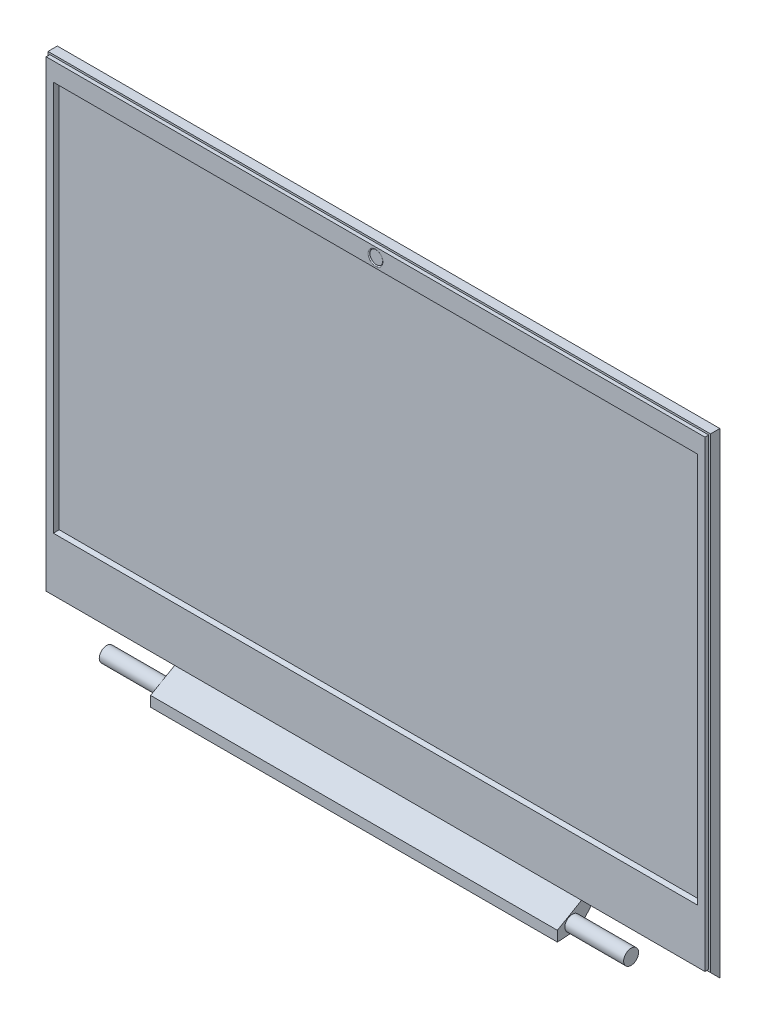
SolidWorks part; units mm, degrees
ref_plane "前视基准面" through (0, 0, 0) normal (0, 0, 1) x (1, 0, 0)
ref_plane "上视基准面" through (0, 0, 0) normal (0, 1, 0) x (1, 0, 0)
ref_plane "右视基准面" through (0, 0, 0) normal (1, 0, 0) x (0, 0, -1)
other "Configuration Table"
sketch "草图1" plane through (0, 0, 0) normal (1, 0, 0) x (0, 0, -1)
  line L0 (0, 0) -> (0, 255)
  line L1 (0, 255) -> (-5, 255)
  line L2 (-5, 255) -> (-5, 5)
  line L3 (-5, 5) -> (0, 0)
  dimension "D1" = 5
  dimension "D2" = 250
  dimension "D3" = 135
extrude "凸台-拉伸1" add sketch "草图1" along normal mid plane 355
sketch "草图3" plane through (0, 0, 0) normal (1, 0, 0) x (0, 0, -1)
  line L0 (0, 0) -> (-6.5838, -7.5269)
  line L1 (-6.5838, -7.5269) -> (-18.557, -8.3272)
  line L2 (-18.557, -8.3272) -> (-18.557, -2.8272)
  line L5 (-18.557, -2.8272) -> (-5, 5)
  line L6 (-5, 255) -> (-5, 5) construction
  line L7 (-5, 5) -> (0, 0)
  dimension "D1" = 135
  dimension "D2" = 5.5
  dimension "D3" = 12
  dimension "D4" = 10
  dimension "D5" = 120
extrude "凸台-拉伸2" add sketch "草图3" along normal mid plane 218
sketch "草图4" plane through (0, 0, 5) normal (0, 0, 1) x (1, 0, 0)
  line L6 (-177.5, 255) -> (-177.5, 5)
  line L7 (-177.5, 5) -> (-109, 5)
  line L8 (-109, 5) -> (109, 5)
  line L9 (109, 5) -> (177.5, 5)
  line L10 (177.5, 5) -> (177.5, 255)
  line L11 (177.5, 255) -> (-177.5, 255)
  line L12 (-177.5, 255) -> (-177.5, 5)
  line L13 (-177.5, 5) -> (-109, 5)
  line L14 (-109, 5) -> (109, 5)
  line L15 (109, 5) -> (177.5, 5)
  line L16 (177.5, 5) -> (177.5, 255)
  line L17 (177.5, 255) -> (-177.5, 255)
  dimension "D1" = 0
extrude "凸台-拉伸3" add sketch "草图4" along normal blind 2
sketch "草图5" plane through (0, 0, 7) normal (0, 0, 1) x (1, 0, 0)
  line L4 (177.5, 255) -> (-177.5, 255)
  line L5 (-177.5, 255) -> (-177.5, 5)
  line L6 (-177.5, 5) -> (177.5, 5)
  line L7 (177.5, 5) -> (177.5, 255)
  line L8 (177.5, 255) -> (-177.5, 255)
  line L9 (-177.5, 255) -> (-177.5, 5)
  line L10 (-177.5, 5) -> (177.5, 5)
  line L11 (177.5, 5) -> (177.5, 255)
  dimension "D1" = 0
extrude "切除-拉伸-薄壁1" cut sketch "草图5" against normal blind 2 flip side to cut thin thin type one direction reverse wall 1
sketch "草图6" plane through (0, 0, 7) normal (0, 0, 1) x (1, 0, 0)
  line L0 (177.5, 255) -> (-177.5, 255) construction
  line L1 (-171.5, 36) -> (171.5, 36)
  line L2 (-171.5, 36) -> (-171.5, 243)
  line L3 (-171.5, 243) -> (171.5, 243)
  line L4 (171.5, 36) -> (171.5, 243)
  line L5 (-176.5, 254) -> (-176.5, 6) construction
  line L6 (176.5, 6) -> (176.5, 254) construction
  line L7 (-176.5, 6) -> (176.5, 6) construction
  dimension "D1" = 12
  dimension "D2" = 5
  dimension "D3" = 5
  dimension "D4" = 30
extrude "切除-拉伸1" cut sketch "草图6" against normal blind 2
chamfer "倒角1" distance 1.154 angle 60 4 edges at (-171.5, 139.5, 7) (0, 243, 7) (171.5, 139.5, 7) (0, 36, 7) first distance on face at (0, 139.5, 7)
sketch "草图7" plane through (0, 0, 7) normal (0, 0, 1) x (1, 0, 0)
  line L0 (0, 254) -> (0, -2.8272) construction
  line L1 (176.5, 254) -> (-176.5, 254) construction
  line L2 (109, -2.8272) -> (-109, -2.8272) construction
  line L4 (176.5, 254) -> (-176.5, 254) construction
  circle A0 centre (0, 249) radius 3.5
  dimension "D1" = 7
  dimension "D2" = 5
extrude "切除-拉伸2" cut sketch "草图7" against normal blind 0.5 contours A0
fillet "圆角1" radius 0.5 1 edges at (3.5, 249, 7)
sketch "草图8" plane through (0, 0, 0) normal (1, 0, 0) x (0, 0, -1)
  line L0 (-18.557, -2.8272) -> (-18.557, -8.3272) construction
  line L1 (-18.557, -8.3272) -> (-6.5838, -7.5269) construction
  circle A0 centre (-10.557, -3.3826) radius 4
  point P6 (-14.0178, -7.9004)
  point P7 (-10.5231, -7.3311)
  dimension "D1" = 8
  dimension "D2" = 8
  dimension "D3" = 4.4
extrude "凸台-拉伸4" add sketch "草图8" along normal mid plane 281
